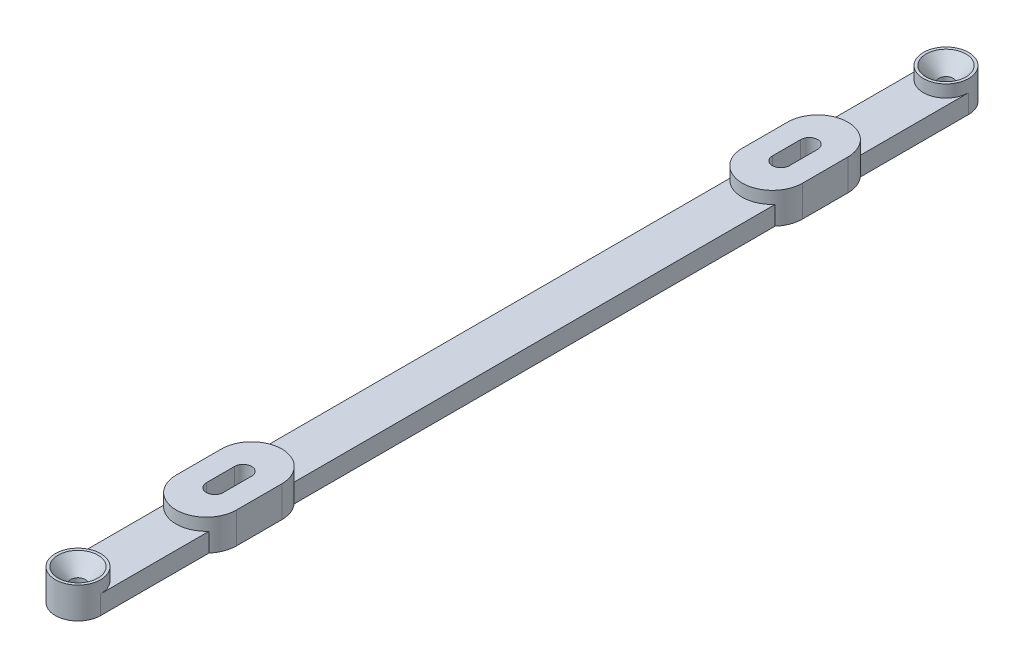
SolidWorks part; units mm, degrees
ref_plane "Front Plane" through (0, 0, 0) normal (0, 0, 1) x (1, 0, 0)
ref_plane "Top Plane" through (0, 0, 0) normal (0, 1, 0) x (1, 0, 0)
ref_plane "Right Plane" through (0, 0, 0) normal (1, 0, 0) x (0, 0, -1)
sketch "Arm Base Sketch" plane through (0, 0, 0) normal (0, 1, 0) x (1, 0, 0)
  line L0 (-6, 115) -> (6, 115)
  line L1 (6, 115) -> (6, 0)
  line L2 (6, 0) -> (-6, 0)
  line L3 (-6, 0) -> (-6, 115)
  point P2 (0, 0)
  dimension "D1" = 115
  dimension "D2" = 12
extrude "Arm Base Extrude" add sketch "Arm Base Sketch" along normal blind 5
sketch "Screw Bases Sketch" plane through (0, 0, 0) normal (0, -1, 0) x (1, 0, 0)
  line L0 (6, -115) -> (-6, -115) construction
  line L1 (0, -81) -> (0, -69) construction
  line L2 (-8, -81) -> (-8, -69)
  line L3 (8, -81) -> (8, -69)
  circle A0 centre (0, -115) radius 6
  arc A1 (-8, -81) -> (8, -81) centre (0, -81) ccw
  arc A2 (8, -69) -> (-8, -69) centre (0, -69) ccw
  point P8 (0, -75)
  dimension "D1" = 16
  dimension "D2" = 12
  dimension "D3" = 75
extrude "Screw Bases Extrude" add sketch "Screw Bases Sketch" against normal blind 8.25
hole_wizard "Power Supply Mounting Slot" positions "Power Supply Mounting Slot Position Sketch" profile "Power Supply Mounting Slot Profile Sketch" size "M4" standard "ANSI Metric" slot yes end condition through all
sketch "Power Supply Mounting Slot Position Sketch" plane through (0, 0, 0) normal (0, -1, 0) x (-1, 0, 0)
  line L0 (0, 81) -> (0, 69) construction
  line L1 (0, 81) -> (0, 69) construction
  point P0 (0, 75)
sketch "Power Supply Mounting Slot Profile Sketch" plane through (0, 0, -75) normal (1, 0, 0) x (0, 0, -1)
  line L0 (0, 0) -> (0, 8.25)
  line L1 (0, 8.25) -> (2.25, 8.25)
  line L3 (2.25, 8.25) -> (2.25, 3.1)
  line L4 (2.25, 3.1) -> (4.5, 3.1)
  line L5 (4.5, 3.1) -> (4.5, 0)
  line L7 (4.5, 0) -> (0, 0)
  line L11 (0, -6.35) -> (0, 107.95) construction
  dimension "Thru Hole Dia." = 4.5
  dimension "Thru Hole Depth" = 8.25
  dimension "C'Bore Dia." = 9
  dimension "C'Bore Depth" = 3.1
hole_wizard "No. 6 Mounting Screws" positions "No. 6 Mounting Screws Position Sketch" profile "No. 6 Mounting Screws Profile Sketch" countersink size "#6" standard "ANSI Inch" end condition through all
sketch "No. 6 Mounting Screws Position Sketch" plane through (0, 8.25, 0) normal (0, 1, 0) x (1, 0, 0)
  circle A0 centre (0, 115) radius 6 construction
  point P0 (0, 115)
sketch "No. 6 Mounting Screws Profile Sketch" plane through (0, 8.25, -115) normal (1, 0, 0) x (0, 0, 1)
  line L0 (0, 0) -> (0, 8.25)
  line L1 (0, 8.25) -> (1.8986, 8.25)
  line L2 (1.8986, 8.25) -> (1.8986, 3.8919)
  line L3 (1.8986, 3.8919) -> (5.2819, 0)
  line L5 (5.2819, 0) -> (0, 0)
  line L6 (-1.8987, 3.8919) -> (-5.2819, 0) construction
  line L11 (0, -6.35) -> (0, 107.95) construction
  dimension "Thru Hole Dia." = 3.7973
  dimension "Thru Hole Depth" = 8.25
  dimension "Near C'Sink Dia." = 10.5637
  dimension "Near C'Sink Angle" = 82
mirror "Mirror" about plane through (6, 5, 0) normal (0, 0, -1) of bodies 104
